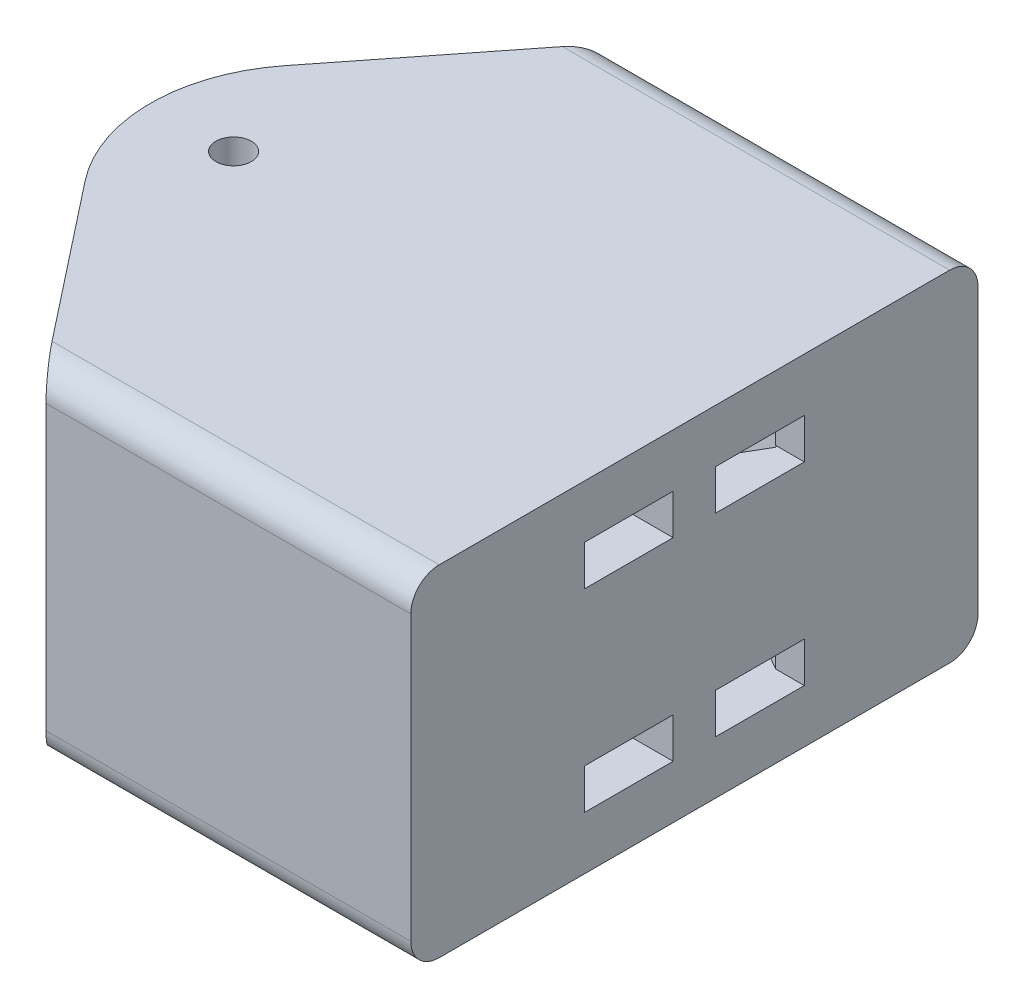
SolidWorks part; units mm, degrees
ref_plane "Front Plane" through (0, 0, 0) normal (0, 0, 1) x (1, 0, 0)
ref_plane "Top Plane" through (0, 0, 0) normal (0, 1, 0) x (1, 0, 0)
ref_plane "Right Plane" through (0, 0, 0) normal (1, 0, 0) x (0, 0, -1)
sketch "Sketch6" plane through (0, 0, 0) normal (0, 1, 0) x (1, 0, 0)
  line L0 (13, 8) -> (13, -8)
  line L3 (0, 0) -> (5.7537, 0) construction
  line L4 (12.2449, 3.0681) -> (5.4384, 7.0188)
  line L5 (4.7064, 8) -> (13, 8)
  line L6 (13, -8) -> (4.7064, -8)
  line L7 (5.2266, -7.1418) -> (12.2449, -3.0681)
  line L8 (12.2449, -3.0681) -> (10.4641, 0)
  line L9 (10.4641, 0) -> (12.2449, 3.0681)
  line L10 (5.2266, -7.1418) -> (2.7076, -7.1418)
  line L11 (2.7076, -7.1418) -> (2.7076, -8)
  line L12 (2.7076, -8) -> (4.7064, -8)
  line L13 (4.7064, 8) -> (2.7076, 8)
  line L14 (2.7076, 8) -> (2.7076, 7.0188)
  line L15 (2.7076, 7.0188) -> (5.4384, 7.0188)
  point P4 (13, 0)
  dimension "D1" = 13
  dimension "D2" = 16
extrude "Boss-Extrude2" add sketch "Sketch6" along normal mid plane 6.6
sketch "Sketch5" plane through (0, 3.3, 0) normal (0, 1, 0) x (1, 0, 0)
  line L0 (2.7076, 8) -> (-1.375, 2.8146)
  line L1 (13, -8) -> (2.7076, -8)
  line L2 (13, -8) -> (13, 8)
  line L3 (13, 8) -> (2.7076, 8)
  line L4 (2.7076, -8) -> (2.7076, 8)
  line L6 (-1.375, -2.8146) -> (2.7076, -8)
  line L7 (0, 0) -> (-4.0649, 0) construction
  line L8 (13, -8) -> (13, 8) construction
  line L9 (13, 8) -> (2.7076, 8) construction
  line L10 (2.7076, -7.1418) -> (2.7076, -8) construction
  circle A0 centre (0, 0) radius 0.5
  arc A1 (-1.375, -2.8146) -> (-1.375, 2.8146) centre (2.2, 0) cw
  point P9 (2.7076, 0)
  dimension "D1" = 1
  dimension "D2" = 4.55
  dimension "D3" = 2.2
extrude "Boss-Extrude3" add sketch "Sketch5" along normal blind 1.5
mirror "Mirror1" about plane through (0, 0, 0) normal (0, 1, 0) of "Boss-Extrude3"
sketch "Sketch7" plane through (13, 0, 0) normal (1, 0, 0) x (0, 0, -1)
  line L0 (-1.0477, 0) -> (0, 0) construction
  line L1 (-3.1, 3.3) -> (-0.6011, 3.3)
  line L2 (-3.1, 3.3) -> (-3.1, 2.1637)
  line L3 (-3.1, 2.1637) -> (-0.6011, 2.1637)
  line L4 (-0.6011, 3.3) -> (-0.6011, 2.1637)
  line L5 (0.6011, 3.3) -> (3.1, 3.3)
  line L6 (0.6011, 3.3) -> (0.6011, 2.1637)
  line L7 (0.6011, 2.1637) -> (3.1, 2.1637)
  line L8 (3.1, 3.3) -> (3.1, 2.1637)
  line L9 (-3.1, -2.1637) -> (-0.6011, -2.1637)
  line L10 (-3.1, -2.1637) -> (-3.1, -3.3)
  line L11 (-3.1, -3.3) -> (-0.6011, -3.3)
  line L12 (-0.6011, -2.1637) -> (-0.6011, -3.3)
  line L13 (0.6011, -2.1637) -> (3.1, -2.1637)
  line L14 (0.6011, -2.1637) -> (0.6011, -3.3)
  line L15 (0.6011, -3.3) -> (3.1, -3.3)
  line L16 (3.1, -2.1637) -> (3.1, -3.3)
  line L17 (0, 0) -> (0, 1.2755) construction
  line L18 (-3.0681, 3.3) -> (-7.1418, 3.3) construction
  dimension "D1" = 6.2
  dimension "D2" = 4.3275
  dimension "D3" = 1.2022
extrude "Cut-Extrude1" cut sketch "Sketch7" against normal through all
fillet "Fillet1" radius 0.8 4 edges at (2.7076, -3.3, 7.5709) (2.7076, 3.3, 7.5709) (2.7076, 3.3, -7.5094) (2.7076, -3.3, -7.5094)
fillet "Fillet2" radius 0.8 4 edges at (7.8538, 4.8, 8) (7.8538, 4.8, -8) (7.8538, -4.8, -8) (7.8538, -4.8, 8)
